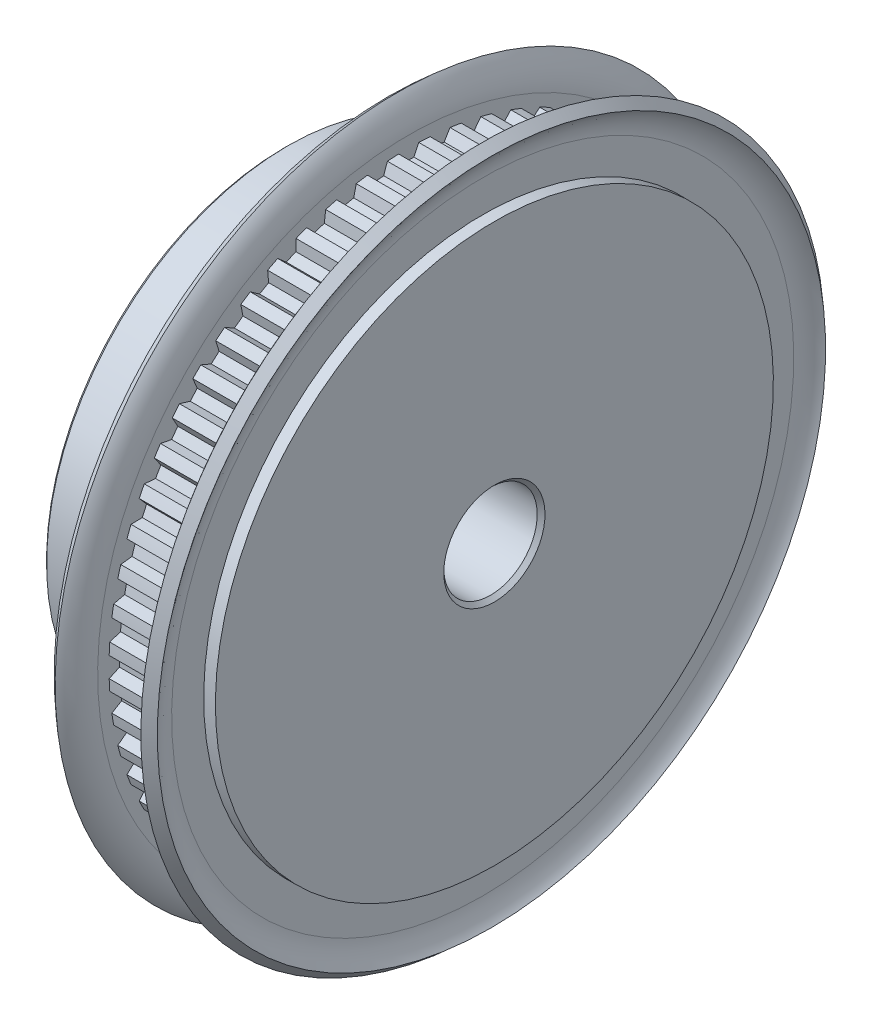
SolidWorks part; units mm, degrees
ref_plane "Front Plane" through (0, 0, 0) normal (0, 0, 1) x (1, 0, 0)
ref_plane "Top Plane" through (0, 0, 0) normal (0, 1, 0) x (1, 0, 0)
ref_plane "Right Plane" through (0, 0, 0) normal (1, 0, 0) x (0, 0, -1)
sketch "Sketch2" plane through (0, 0, 0) normal (1, 0, 0) x (0, 0, -1)
  line L3 (0, 0) -> (0, 18.5745) construction
  line L6 (0, -19.0825) -> (0, -19.4) construction
  line L7 (-0.5715, 19.0739) -> (-0.3372, 18.5714)
  line L8 (0.5715, 19.0739) -> (0.3372, 18.5714)
  line L9 (-0.5715, 19.0739) -> (-0.6445, 19.2305)
  line L10 (0.5715, 19.0739) -> (0.6445, 19.2305)
  line L12 (-0.3372, 18.5714) -> (0.3372, 18.5714)
  line L14 (0, 19.0825) -> (0, 19.4) construction
  line L15 (0, 0) -> (0, -1.143) construction
  circle A0 centre (0, 0) radius 19.4 construction
  circle A1 centre (0, 0) radius 18.5745 construction
  circle A2 centre (0, 0) radius 19.0825 construction
  arc A7 (0.6445, 19.2305) -> (-0.6445, 19.2305) centre (0, 0) ccw
  point P5 (0, 19.2412)
  dimension "D3" = 0.3175
  dimension "D1" = 50
sketch "Sketch1" plane through (0, 0, 0) normal (0, 0, 1) x (1, 0, 0)
  line L0 (-6.75, 0) -> (6.75, 0) construction
  line L1 (-6.75, 3) -> (6.75, 3)
  line L2 (-6.75, 3) -> (-6.75, 15.5)
  line L3 (-0.25, 21.95) -> (0.5, 21.95)
  line L4 (1.25, 19.4) -> (1.25, 19.9715)
  line L5 (1.25, 20.543) -> (1.25, 19.4) construction
  line L6 (1.25, 19.4) -> (5.25, 19.4)
  line L7 (5.25, 19.4) -> (5.25, 19.9715)
  line L8 (5.25, 19.4) -> (6.75, 19.4) construction
  line L9 (6, 21.95) -> (6.75, 21.95)
  line L10 (6.75, 21.95) -> (6.75, 3)
  line L11 (6, 19.4) -> (6, 21.95) construction
  line L12 (-3.5, 15.5) -> (-3.5, 3) construction
  line L13 (-0.25, 21.95) -> (-0.25, 15.5)
  line L14 (-0.25, 15.5) -> (-6.75, 15.5)
  arc A0 (5.25, 19.9715) -> (6, 21.95) centre (8.2346, 19.9715) cw
  arc A1 (1.25, 19.9715) -> (0.5, 21.95) centre (-1.7346, 19.9715) ccw
  point P20 (3.25, 19.4)
  dimension "Bore Size" = 6
  dimension "Overall Width" = 13.5
  dimension "Inside Width" = 4
  dimension "OD" = 43.9
  dimension "D2" = 38.8
  dimension "D3" = 1.143
  dimension "D4" = 0.5715
  dimension "Outside Width" = 7
revolve "Revolve1" add sketch "Sketch1" angle 360 mid plane about L0
sketch "Sketch4" plane through (1.25, 0, 0) normal (1, 0, 0) x (0, 0, -1)
  circle A0 centre (0, 0) radius 19.2412
  circle A2 centre (0, 0) radius 19.4
  circle A3 centre (0, 0) radius 19.4 construction
extrude "Cut-Extrude2" cut sketch "Sketch4" along normal up to surface (4 mm away) up to face at (5.25, -19.4, 0)
sketch "Sketch3" plane through (1.25, 0, 0) normal (1, 0, 0) x (0, 0, -1)
  line L2 (-0.5715, 19.0739) -> (-0.3372, 18.5714) construction
  line L3 (-0.3372, 18.5714) -> (0.3372, 18.5714) construction
  line L4 (0.5715, 19.0739) -> (0.3372, 18.5714) construction
  line L5 (-0.6445, 19.2305) -> (-0.3372, 18.5714)
  line L6 (-0.3372, 18.5714) -> (0.3372, 18.5714)
  line L7 (0.6445, 19.2305) -> (0.3372, 18.5714)
  arc A1 (0.6445, 19.2305) -> (-0.6445, 19.2305) centre (0, 0) ccw construction
  arc A2 (0.6445, 19.2305) -> (-0.6445, 19.2305) centre (0, 0) ccw
extrude "Cut-Extrude1" cut sketch "Sketch3" along normal up to surface (4 mm away)
pattern_circular "CirPattern1" count 60 over 360 about axis through (0, 0, 0) along (1, 0, 0) of "Cut-Extrude1"
sketch "Sketch6" plane through (0, 0, 0) normal (0, 1, 0) x (1, 0, 0)
  line L0 (-6.75, 0) -> (-5, 0) construction
  line L2 (-0.25, 0) -> (-2, 0) construction
  line L5 (-3.5, 0) -> (-4.5607, -1.0607) construction
  circle A0 centre (-3.5, 0) radius 1.5 construction
  circle A1 centre (-3.5, 0) radius 1.6
  dimension "D1" = 0.1
  dimension "D2" = 45
  dimension "SS Dia" = 3
extrude "Cut-Extrude3" cut sketch "Sketch6" along normal through all
sketch "Sketch7" plane through (0, 0, 0) normal (0, 0, 1) x (1, 0, 0)
  line L0 (-4.746, 15.5) -> (-3.5, 15.5)
  line L1 (-5, 15.246) -> (-5, 3.635)
  line L2 (-5, 3.635) -> (-4.746, 3.381)
  line L3 (-4.746, 3.381) -> (-3.5, 3.381)
  line L4 (-3.5, 3.381) -> (-3.5, 15.5) construction
  line L5 (-0.25, 15.5) -> (-6.75, 15.5) construction
  line L6 (-5, 15.246) -> (-4.746, 15.5)
  line L8 (-3.5, 15.5) -> (-3.5, 3.381)
  point P0 (-5, 15.5)
  point P4 (-5, 3.381)
  dimension "D2" = 0.381
revolve "Revolve2" add sketch "Sketch7" angle 360 mid plane about L4
sketch "Sketch8" plane through (0, 15.5, 0) normal (0, 1, 0) x (1, 0, 0)
  line L0 (-3.5, 0) -> (-3.5, 1.5) construction
  line L1 (-3.5, 0.866) -> (-4.25, 0.433)
  line L2 (-4.25, 0.433) -> (-4.25, -0.433)
  line L3 (-4.25, -0.433) -> (-3.5, -0.866)
  line L4 (-3.5, -0.866) -> (-2.75, -0.433)
  line L5 (-2.75, -0.433) -> (-2.75, 0.433)
  line L6 (-2.75, 0.433) -> (-3.5, 0.866)
  circle A0 centre (-3.5, 0) radius 0.75 construction
  circle A1 centre (-3.5, 0) radius 1.5 construction
  point P16 (-3.5, 0.75)
extrude "Cut-Extrude4" cut sketch "Sketch8" against normal blind 1.016
pattern_circular "CirPattern2" count 2 over 90 about axis through (-6.75, 0, 0) along (-1, 0, 0) of "Cut-Extrude3"
pattern_circular "CirPattern3" count 2 over 90 about axis through (0, 0, 0) along (1, 0, 0) of bodies 107
sketch "Sketch5" plane through (0, 0, 0) normal (0, 0, 1) x (1, 0, 0)
  line L1 (5.25, 19.9715) -> (5.25, -19.9715) construction
  line L5 (1.25, -19.9715) -> (1.25, 19.9715) construction
  line L6 (1.25, -19.9715) -> (1.25, 19.9715) construction
  line L7 (5.25, 19.9715) -> (5.25, -19.9715) construction
  line L8 (-5, 0) -> (-3.5, 0) construction
  line L9 (-3.5, 0) -> (-4.5607, -1.0607) construction
  circle A0 centre (-3.5, 0) radius 1.5 construction
  circle A1 centre (-3.5, 0) radius 1.5 construction
  point P0 (5.25, 0)
  point P10 (-4.5607, -1.0607)
  dimension "D1" = 45
sketch "Sketch10" plane through (0, 0, 0) normal (0, 1, 0) x (1, 0, 0)
  line L0 (-0.25, 21.95) -> (-0.25, -21.95) construction
  line L1 (-0.25, 21.95) -> (-0.25, -21.95)
chamfer "Chamfer1" distance 0.25 angle 45 3 edges at (-6.75, -15.5, 0) (6.75, -3, 0) (-6.75, -3, 0)
sketch "Sketch9" plane through (0, 0, 0) normal (0, 0, 1) x (1, 0, 0)
  line L0 (-6.75, 0) -> (6.75, 0) construction
  line L3 (6, 21.95) -> (6.5615, 21.4528)
  line L4 (6, 19.9715) -> (6, 17.9124)
  line L5 (1.25, 17.9124) -> (6, 17.9124) construction
  line L6 (6, 17.9124) -> (6.75, 17.9124)
  line L7 (6.75, 21.95) -> (6.75, 3) construction
  line L8 (6.75, 17.9124) -> (6.75, 21.95)
  line L9 (6, 21.95) -> (6.3296, 22.3222)
  line L10 (6.3296, 22.3222) -> (6.75, 21.95)
  line L11 (1.25, 19.2305) -> (1.25, 18.5714) construction
  line L12 (1.25, 18.5714) -> (1.25, 17.9124) construction
  arc A0 (6.5615, 21.4528) -> (6, 19.9715) centre (8.2346, 19.9715) ccw
  arc A2 (6, 21.95) -> (5.25, 19.9715) centre (8.2346, 19.9715) ccw construction
revolve "Cut-Revolve1" cut sketch "Sketch9" angle 360 about L0
ref_plane "Plane1" through (3.25, 0, 0) normal (1, 0, 0) x (0, 0, -1)
mirror "Mirror1" about plane through (3.25, 0, 0) normal (1, 0, 0) of "Cut-Revolve1"
equation "\"D3@Sketch2\" = (\"hs@Sketch2\"-\"ht@Sketch2\")/2"
equation "\"D2@Sketch1\" = \"PD@Sketch2\""
equation "\"D3@Sketch1\" = \"hs@Sketch2\""
equation "\"D4@Sketch1\" = \"D3@Sketch1\"/2"
